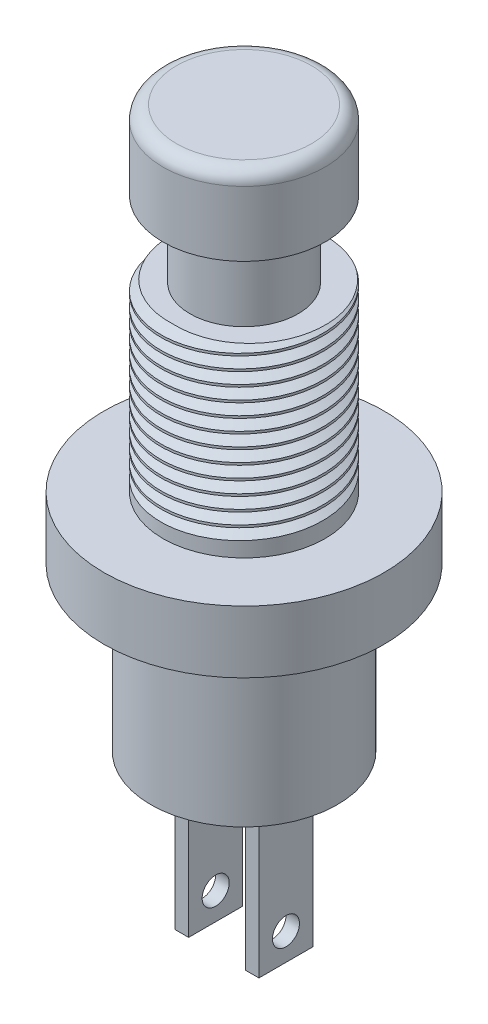
SolidWorks part; units mm, degrees
ref_plane "Front Plane" through (0, 0, 0) normal (0, 0, 1) x (1, 0, 0)
ref_plane "Top Plane" through (0, 0, 0) normal (0, 1, 0) x (1, 0, 0)
ref_plane "Right Plane" through (0, 0, 0) normal (1, 0, 0) x (0, 0, -1)
sketch "Sketch1" plane through (0, 0, 0) normal (0, 1, 0) x (1, 0, 0)
  circle A0 centre (0, 0) radius 3.45
  dimension "D1" = 6.9
extrude "Body bottom" add sketch "Sketch1" along normal blind 6
sketch "Sketch2" plane through (0, 0, 0) normal (0, -1, 0) x (1, 0, 0)
  line L1 (-1.55, 1) -> (-1.05, 1)
  line L2 (-1.55, 1) -> (-1.55, -1)
  line L3 (-1.55, -1) -> (-1.05, -1)
  line L4 (-1.05, 1) -> (-1.05, -1)
  line L5 (-1.55, 1) -> (-1.05, -1) construction
  line L6 (-1.55, -1) -> (-1.05, 1) construction
  point P4 (-1.3, 0)
  dimension "D1" = 2
  dimension "D2" = 0.5
  dimension "D3" = 1.3
extrude "Leg 1" add sketch "Sketch2" along normal blind 6
sketch "Sketch3" plane through (0, 0, 0) normal (0, -1, 0) x (1, 0, 0)
  line L1 (1.55, -1) -> (1.05, -1)
  line L2 (1.55, -1) -> (1.55, 1)
  line L3 (1.55, 1) -> (1.05, 1)
  line L4 (1.05, -1) -> (1.05, 1)
  line L5 (1.55, -1) -> (1.05, 1) construction
  line L6 (1.55, 1) -> (1.05, -1) construction
  point P4 (1.3, 0)
  dimension "D1" = 2
  dimension "D2" = 0.5
  dimension "D3" = 1.3
extrude "Leg 2" add sketch "Sketch3" along normal blind 6
sketch "Sketch4" plane through (1.55, 0, 0) normal (1, 0, 0) x (0, 0, -1)
  line L0 (1, -6) -> (-1, -6) construction
  line L1 (1, -6) -> (1, 0) construction
  circle A0 centre (0, -5) radius 0.5
  dimension "D1" = 1
  dimension "D2" = 1
  dimension "D3" = 1
extrude "Cut-Extrude1" cut sketch "Sketch4" against normal blind 4.9972
sketch "Sketch5" plane through (0, 6, 0) normal (0, 1, 0) x (1, 0, 0)
  circle A0 centre (0, 0) radius 5.18
  dimension "D1" = 10.36
extrude "Boss-Extrude4" add sketch "Sketch5" along normal blind 2.3
sketch "Sketch6" plane through (0, 8.3, 0) normal (0, 1, 0) x (1, 0, 0)
  circle A0 centre (0, 0) radius 3
  dimension "D1" = 6
extrude "Boss-Extrude5" add sketch "Sketch6" along normal blind 6.7
sketch "Sketch7" plane through (0, 15, 0) normal (0, 1, 0) x (1, 0, 0)
  circle A0 centre (0, 0) radius 3
  dimension "D1" = 6
curve "Helix/Spiral1" pitch 0.5 height 6.25 radius 3 centre (0, 15, 0) axis (0, -1, 0) start towards (0, 0, 1)
sketch "Sketch16" plane through (0, 15, 0) normal (0, 1, 0) x (1, 0, 0)
  circle A0 centre (0, 0) radius 2
  dimension "D1" = 4
extrude "Button cap 2" add sketch "Sketch16" along normal blind 2.8
sketch "Sketch17" plane through (0, 17.8, 0) normal (0, 1, 0) x (1, 0, 0)
  circle A0 centre (0, 0) radius 3
  dimension "D1" = 6
extrude "Button cap" add sketch "Sketch17" along normal blind 2.9
fillet "Fillet1" radius 0.5 1 edges at (0, 20.7, 3) type face fillet first side face at (0, 20.7, 3) second side face at (0, 20.7, 3)
sketch "Sketch20" plane through (0, 0, 0) normal (1, 0, 0) x (0, 0, -1)
  line L1 (-2.6423, 15) -> (-3.1788, 15.3098)
  line L2 (-3.1788, 15.3098) -> (-3.1788, 14.6902)
  line L3 (-3.1788, 14.6902) -> (-2.6423, 15)
  circle A0 centre (-3, 15) radius 0.1788 construction
sweep "Cut-Sweep4" cut profiles "Sketch20" path "Helix/Spiral1" align with end faces yes
